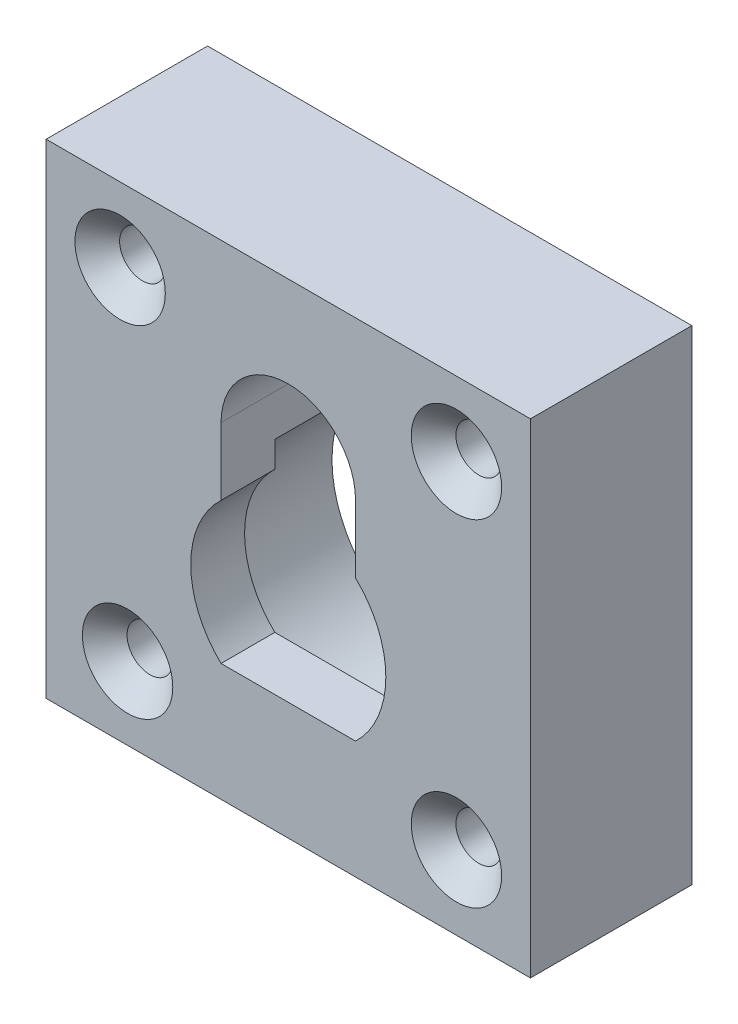
SolidWorks part; units mm, degrees
ref_plane "Front Plane" through (0, 0, 0) normal (0, 0, 1) x (1, 0, 0)
ref_plane "Top Plane" through (0, 0, 0) normal (0, 1, 0) x (1, 0, 0)
ref_plane "Right Plane" through (0, 0, 0) normal (1, 0, 0) x (0, 0, -1)
sketch "Sketch1" plane through (0, 0, 0) normal (0, 0, 1) x (1, 0, 0)
  line L1 (18, -18) -> (-18, -18)
  line L2 (18, -18) -> (18, 18)
  line L3 (18, 18) -> (-18, 18)
  line L4 (-18, -18) -> (-18, 18)
  line L5 (18, -18) -> (-18, 18) construction
  line L6 (18, 18) -> (-18, -18) construction
  point P0 (0, 0)
  dimension "D1" = 36
  dimension "D2" = 36
extrude "Boss-Extrude1" add sketch "Sketch1" along normal blind 12
sketch "Sketch2" plane through (0, 0, 0) normal (0, 0, -1) x (-1, 0, 0)
  line L1 (18, -18) -> (-18, -18) construction
  line L3 (18, 18) -> (18, -18) construction
  circle A0 centre (0, -4) radius 8.75
  point P2 (0, -5.6969)
  dimension "D1" = 17.5
  dimension "D3" = 5.25
  dimension "D4" = 9.25
  dimension "D2" = 4
extrude "Cut-Extrude1" cut sketch "Sketch2" against normal blind 8
sketch "Sketch3" plane through (0, 0, 8) normal (0, 0, -1) x (-1, 0, 0)
  line L0 (-5, 1.25) -> (5, 1.25)
  line L1 (-5, -9.25) -> (5, -9.25)
  line L2 (-7.25, -4) -> (7.25, -4) construction
  arc A0 (-5, 1.25) -> (-5, -9.25) centre (0, -4) ccw
  circle A1 centre (0, -4) radius 8.75 construction
  arc A2 (5, -9.25) -> (5, 1.25) centre (0, -4) ccw
  dimension "D1" = 14.5
  dimension "D2" = 10.5
extrude "Cut-Extrude2" cut sketch "Sketch3" against normal up to next
sketch "Sketch4" plane through (0, 0, 0) normal (0, 0, -1) x (-1, 0, 0)
  line L0 (5, 1.25) -> (-5, 1.25) construction
  line L1 (-5, 6.25) -> (-5, 1.25)
  line L2 (5, 6.25) -> (5, 1.25)
  line L3 (-5, 1.25) -> (5, 1.25)
  arc A0 (5, 6.25) -> (-5, 6.25) centre (0, 6.25) ccw
  dimension "D1" = 10
extrude "Cut-Extrude3" cut sketch "Sketch4" against normal up to next
hole_wizard "CSK for M3 SFHCS1" positions "Sketch7" profile "Sketch6" countersink size "M3" standard "ANSI Metric" end condition through all
sketch "Sketch7" plane through (0, 0, 12) normal (0, 0, 1) x (1, 0, 0)
  line L0 (-12.5, 12.5) -> (12.5, 12.5) construction
  line L1 (12.5, 12.5) -> (12.5, -12.5) construction
  point P0 (-11.9466, -12.5779)
  point P2 (12.5, -12.5)
  point P4 (12.5, 12.5)
  point P6 (-12.5, 12.5)
  point P13 (0, 12.5)
  point P15 (12.5, 0)
  dimension "D1" = 25
  dimension "D2" = 25
sketch "Sketch6" plane through (-11.9466, -12.5779, 12) normal (1, 0, 0) x (0, -1, 0)
  line L0 (0, 0) -> (0, 12)
  line L1 (0, 12) -> (1.7, 12)
  line L2 (1.7, 12) -> (1.7, 1.66)
  line L3 (1.7, 1.66) -> (3.36, 0)
  line L5 (3.36, 0) -> (0, 0)
  line L6 (-1.7, 1.66) -> (-3.36, 0) construction
  line L11 (0, -6.35) -> (0, 107.95) construction
  dimension "Thru Hole Dia." = 3.4
  dimension "Thru Hole Depth" = 12
  dimension "Near C'Sink Dia." = 6.72
  dimension "Near C'Sink Angle" = 90
